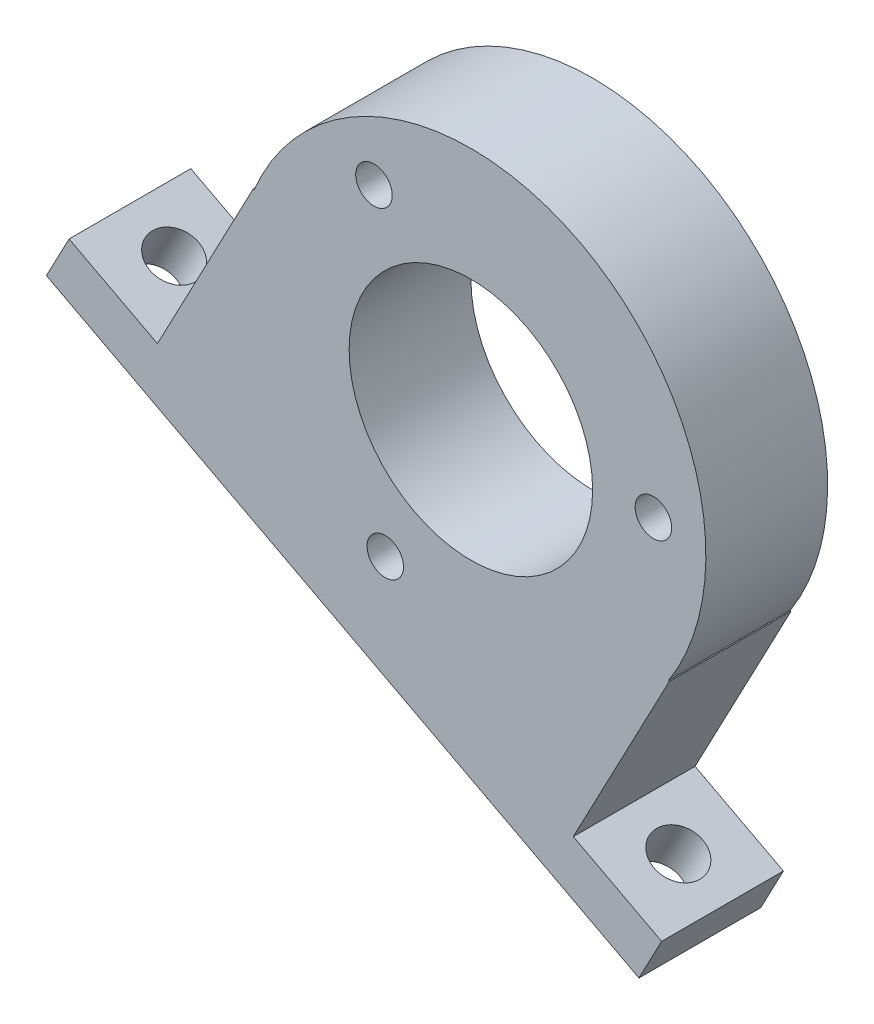
SolidWorks part; units mm, degrees
ref_plane "Front Plane" through (0, 0, 0) normal (0, 0, 1) x (1, 0, 0)
ref_plane "Top Plane" through (0, 0, 0) normal (0, 1, 0) x (1, 0, 0)
ref_plane "Right Plane" through (0, 0, 0) normal (1, 0, 0) x (0, 0, -1)
sketch "Sketch1" plane through (0, 0, 0) normal (0, 0, 1) x (1, 0, 0)
  circle A3 centre (-14.1274, 5.3793) radius 10
  circle A4 centre (-14.1274, 5.3793) radius 19.3
  circle A5 centre (0.863, 5.9165) radius 1.5
  circle A6 centre (-22.0878, 18.0927) radius 1.5
  circle A7 centre (-21.1574, -7.8714) radius 1.5
extrude "Boss-Extrude1" add sketch "Sketch1" along normal blind 10
sketch "Sketch2" plane through (-14.1757, -26.9186, 0) normal (-0.466, -0.8848, 0) x (0.8848, -0.466, 0)
  line L0 (-37.5066, 25) -> (7.4934, 25) construction
  line L1 (-42.5066, 25) -> (12.4934, 25)
  line L2 (-42.5066, 25) -> (-42.5066, 0)
  line L3 (-42.5066, 0) -> (12.4934, 0)
  line L4 (12.4934, 25) -> (12.4934, 0)
  line L5 (-42.5066, 25) -> (12.4934, 0) construction
  line L6 (-42.5066, 0) -> (12.4934, 25) construction
  line L7 (-34.3066, 0) -> (4.2934, 0) construction
  line L11 (-37.5066, 80.75) -> (-37.5066, 25) construction
  line L15 (12.4934, 0) -> (-42.5066, 0)
  line L16 (12.4934, 0) -> (12.4934, 10)
  line L17 (12.4934, 10) -> (-42.5066, 10)
  line L18 (-42.5066, 0) -> (-42.5066, 10)
  line L19 (12.4934, 0) -> (-42.5066, 10) construction
  line L20 (12.4934, 10) -> (-42.5066, 0) construction
  point P4 (-15.0066, 12.5)
  point P13 (-15.0066, 5)
  dimension "D1" = 0
  dimension "D2" = 55
  dimension "D3" = 5
  dimension "D4" = 10
extrude "Boss-Extrude2" add sketch "Sketch2" against normal blind 50 contours L4 L17 L2 L3 region at (-27.4537, -19.9263, 5)
sketch "Sketch4" plane through (0, 0, 0) normal (0, 0, -1) x (-1, 0, 0)
  line L0 (-9.4258, -8.9137) -> (39.2387, 16.7137)
  line L1 (-20.1762, 11.5005) -> (3.1214, -32.74) construction
  line L2 (28.4883, 37.1279) -> (51.7859, -7.1125) construction
  line L3 (51.7859, -7.1125) -> (3.1214, -32.74) construction
  line L4 (39.2387, 16.7137) -> (28.4883, 37.1279)
  line L5 (28.4883, 37.1279) -> (-20.1762, 11.5005)
  line L6 (-20.1762, 11.5005) -> (-9.4258, -8.9137)
  line L7 (47.1264, 1.7355) -> (39.871, -2.0853)
  line L8 (39.871, -2.0853) -> (31.9833, 12.8929)
  line L9 (-2.1704, -5.0929) -> (5.7173, -20.0711)
  line L10 (5.7173, -20.0711) -> (-1.5381, -23.8919)
  line L11 (51.7859, -7.1125) -> (3.1214, -32.74)
  line L12 (51.7859, -7.1125) -> (48.9902, -1.8037)
  line L13 (3.1214, -32.74) -> (0.3257, -27.4311)
  line L14 (48.9902, -1.8037) -> (0.3257, -27.4311)
  circle A0 centre (14.1274, 5.3793) radius 19.3
  circle A1 centre (14.1274, 5.3793) radius 19.3 construction
  line M2 (3.1214, -32.74) -> (51.7859, -7.1125)
  line M3 (51.7859, -7.1125) -> (28.4883, 37.1279)
  line M4 (28.4883, 37.1279) -> (-20.1762, 11.5005)
  line M5 (-20.1762, 11.5005) -> (3.1214, -32.74)
  dimension "D1" = 10
  dimension "D2" = 10
  dimension "D3" = 6
extrude "Cut-Extrude1" cut sketch "Sketch4" against normal blind 50 contours A0 L0 M3 M4 M5 | L8 L7 L0 M3 | L10 L9 L0 M5 | L14 M3 M5 M2 region at (14.1359, 1.6436, 0) region at (1.8542, -14.4924, 0) region at (-26.0558, -17.2718, 0) region at (-39.5548, 7.3142, 0)
sketch "Sketch5" plane through (-9.5162, -18.0705, 0) normal (0.466, 0.8848, 0) x (0.8848, -0.466, 0)
  line L0 (12.4934, -10) -> (4.2934, -10) construction
  line L1 (-34.3066, 0) -> (-42.5066, 0)
  line L2 (-34.3066, 0) -> (-34.3066, -10)
  line L3 (-34.3066, -10) -> (-42.5066, -10)
  line L4 (-42.5066, 0) -> (-42.5066, -10)
  line L5 (-34.3066, 0) -> (-42.5066, -10) construction
  line L6 (-34.3066, -10) -> (-42.5066, 0) construction
  line L7 (12.4934, 0) -> (4.2934, 0)
  line L8 (12.4934, 0) -> (12.4934, -10)
  line L9 (12.4934, -10) -> (4.2934, -10)
  line L10 (4.2934, 0) -> (4.2934, -10)
  line L11 (12.4934, 0) -> (4.2934, -10) construction
  line L12 (12.4934, -10) -> (4.2934, 0) construction
  circle A0 centre (-38.4066, -5) radius 2
  circle A1 centre (8.3934, -5) radius 2
  point P4 (-38.4066, -5)
  point P11 (8.3934, -5)
  dimension "D1" = 4
  dimension "D2" = 4
extrude "Cut-Extrude2" cut sketch "Sketch5" against normal blind 50 contours A0 | A1 region at (-43.4987, -0.1749, 5) region at (-2.0896, -21.9815, 5)
extrude "Cut-Extrude3" cut sketch "Sketch1<2>" along normal blind 50 contours A3 | A7 | A6 | A5 region at (-14.1274, 5.3793, 0)
sketch "Sketch1<2>" plane through (0, 0, 0) normal (0, 0, 1) x (1, 0, 0) same geometry as "Sketch1"
